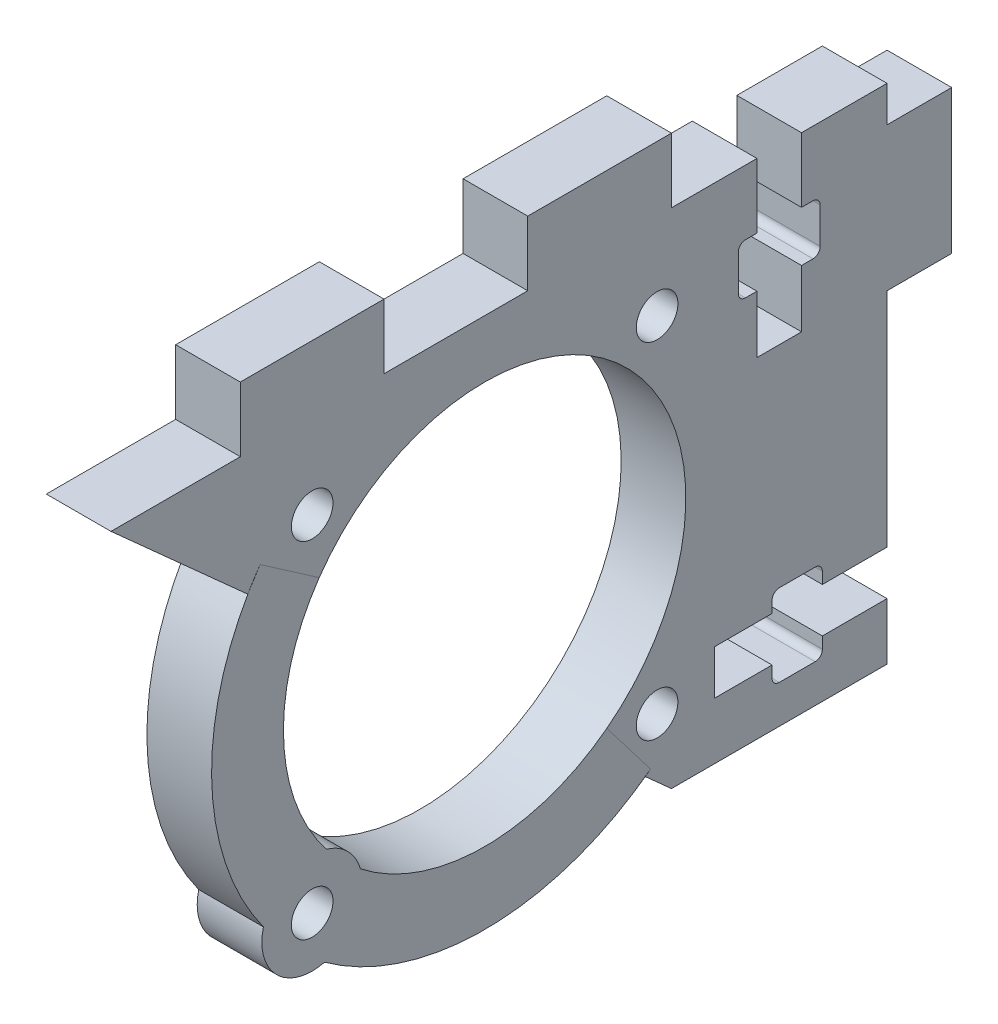
SolidWorks part; units mm, degrees
ref_plane "Front Plane" through (0, 0, 0) normal (0, 0, 1) x (1, 0, 0)
ref_plane "Top Plane" through (0, 0, 0) normal (0, 1, 0) x (1, 0, 0)
ref_plane "Right Plane" through (0, 0, 0) normal (1, 0, 0) x (0, 0, -1)
sketch "Sketch1" plane through (0, 0, 0) normal (1, 0, 0) x (0, 0, -1)
  line L0 (0, 0) -> (0, -35)
  line L1 (0, -35) -> (-54, 0)
  line L2 (-54, 0) -> (0, 0)
  dimension "D1" = 35
  dimension "D2" = 54
extrude "Boss-Extrude1" add sketch "Sketch1" along normal blind 4.5
sketch "Sketch2" plane through (4.5, 0, 0) normal (1, 0, 0) x (0, 0, -1)
  line L0 (0, -35) -> (0, 0) construction
  line L1 (-4.5, -2.5) -> (4.5, -2.5)
  line L2 (-4.5, -2.5) -> (-4.5, -12.5)
  line L3 (-4.5, -12.5) -> (4.5, -12.5)
  line L4 (4.5, -2.5) -> (4.5, -12.5)
  line L5 (-4.5, -2.5) -> (4.5, -12.5) construction
  line L6 (-4.5, -12.5) -> (4.5, -2.5) construction
  line L7 (0, 0) -> (-54, 0) construction
  point P0 (0, -7.5)
  dimension "D1" = 10
  dimension "D2" = 7.5
  dimension "D3" = 4.5
extrude "Boss-Extrude2" add sketch "Sketch2" against normal through all
sketch "Sketch3" plane through (4.5, 0, 0) normal (1, 0, 0) x (0, 0, -1)
  line L0 (0, -35) -> (-15, -35)
  line L1 (0, -25) -> (-54, 0)
  line L4 (0, -35) -> (0, -12.5) construction
  line L5 (0, -25) -> (0, -35)
  line L6 (-54, 0) -> (-15, -35)
  dimension "D1" = 15
  dimension "D2" = 10
extrude "Boss-Extrude3" add sketch "Sketch3" against normal through all
sketch "Sketch4" plane through (4.5, 0, 0) normal (1, 0, 0) x (0, 0, -1)
  line L0 (0, -29.5) -> (-12, -29.5) construction
  line L1 (0, -35) -> (0, -12.5) construction
  line L2 (0, -27.95) -> (-12, -27.95) construction
  line L3 (-12, -27.95) -> (-12, -31.05) construction
  line L4 (0, -31.05) -> (0, -27.95)
  line L5 (0, -27.95) -> (-4.5, -27.95)
  line L6 (-4.5, -27.95) -> (-4.5, -27.15)
  line L7 (-5, -26.65) -> (-7.5, -26.65)
  line L8 (-8, -27.15) -> (-8, -27.95)
  line L9 (-8, -27.95) -> (-12, -27.95)
  line L10 (-12, -27.95) -> (-12, -31.05)
  line L12 (0, -31.05) -> (-12, -31.05) construction
  line L13 (-8, -31.05) -> (-12, -31.05)
  line L14 (-8, -31.85) -> (-8, -31.05)
  line L15 (-5, -32.35) -> (-7.5, -32.35)
  line L16 (-4.5, -31.05) -> (-4.5, -31.85)
  line L17 (0, -31.05) -> (-4.5, -31.05)
  line L18 (4.5, -12.5) -> (4.5, -2.5) construction
  line L19 (0, -18.5) -> (-33.3857, -18.5) construction
  line L20 (-54, 0) -> (-15, -35) construction
  line L37 (0, -31.05) -> (-12, -31.05) construction
  arc A0 (-8, -31.85) -> (-7.5, -32.35) centre (-7.5, -31.85) ccw
  arc A1 (-5, -32.35) -> (-4.5, -31.85) centre (-5, -31.85) ccw
  arc A2 (-4.5, -27.15) -> (-5, -26.65) centre (-5, -27.15) ccw
  arc A3 (-7.5, -26.65) -> (-8, -27.15) centre (-7.5, -27.15) ccw
  point P10 (4.5, -7.5)
  point P20 (-8, -32.35)
  point P23 (-4.5, -32.35)
  point P26 (-4.5, -26.65)
  point P29 (-8, -26.65)
  dimension "D7" = 0.5
  dimension "D1" = 12
  dimension "D2" = 1.55
  dimension "D3" = 2.85
  dimension "D4" = 3.5
  dimension "D5" = 8
  dimension "D6" = 22
extrude "Cut-Extrude1" cut sketch "Sketch4" against normal through all
sketch "Sketch5" plane through (4.5, 0, 0) normal (1, 0, 0) x (0, 0, -1)
  line L0 (0, 0) -> (-54, 0) construction
  line L1 (-25, 4.5) -> (-15, 4.5)
  line L2 (-25, 4.5) -> (-25, 0)
  line L3 (0, 0) -> (-54, 0) construction
  line L4 (-15, 4.5) -> (-15, 0)
  line L5 (-25, 4.5) -> (-20, 0) construction
  line L6 (-20, 0) -> (-15, 4.5) construction
  line L7 (-30, 0) -> (-30, 4.5) construction
  line L8 (-40, 0) -> (-45, 4.5) construction
  line L9 (-35, 4.5) -> (-40, 0) construction
  line L10 (-45, 4.5) -> (-45, 0)
  line L12 (-35, 4.5) -> (-35, 0)
  line L13 (-35, 4.5) -> (-45, 4.5)
  line L14 (-20, 0) -> (-15, 4.5) construction
  line L15 (-15, 0) -> (-25, 0)
  line L16 (-35, 0) -> (-45, 0)
  point P0 (-20, 0)
  point P14 (-40, 0)
  dimension "D3" = 4.5
  dimension "D1" = 20
  dimension "D2" = 10
  dimension "D4" = 20
  dimension "D5" = 5
extrude "Boss-Extrude4" add sketch "Sketch5" against normal through all
sketch "Sketch8" [suppressed] plane through (4.5, 0, 0) normal (1, 0, 0) x (0, 0, -1)
  line L0 (-15, -30) -> (-27, -30) construction
  line L1 (-15, -35) -> (-27, -35)
  line L2 (-15, -25) -> (-27, -25)
  line L3 (-15, -35) -> (0, -35) construction
  line L4 (-15, -25) -> (-15, -35)
  arc A1 (-27, -25) -> (-27, -35) centre (-27, -30) ccw
  dimension "D5" = 5
  dimension "D1" = 0
  dimension "D2" = 12
  dimension "D3" = 0
  dimension "D4" = 10
extrude "Boss-Extrude5" [suppressed] add sketch "Sketch8" against normal up to surface (4.5 mm away) up to face at (0, -17.3125, 11.9375)
sketch "Sketch9" [suppressed] plane through (4.5, 0, 0) normal (1, 0, 0) x (0, 0, -1)
  line L0 (-27, -30) -> (-22, -30) construction
  line L1 (-27, -27) -> (-22, -27)
  line L2 (-27, -33) -> (-22, -33)
  arc A0 (-27, -27) -> (-27, -33) centre (-27, -30) ccw
  arc A1 (-22, -33) -> (-22, -27) centre (-22, -30) ccw
  point P3 (-24.5, -30)
  dimension "D1" = 3
  dimension "D2" = 5
extrude "Cut-Extrude3" [suppressed] cut sketch "Sketch9" against normal through all
sketch "Sketch10" plane through (0, 0, 0) normal (-1, 0, 0) x (0, 0, 1)
  line L0 (15, -35) -> (54, -12)
  line L1 (54, -12) -> (54, 0)
  line L3 (54, 0) -> (15, -35)
  dimension "D1" = 12
extrude "Boss-Extrude6" [suppressed] add sketch "Sketch10" against normal through all
sketch "Sketch6" plane through (4.5, 0, 0) normal (1, 0, 0) x (0, 0, -1)
  line L0 (-30, 0) -> (-30, -11) construction
  line L1 (-25, 0) -> (-35, 0) construction
  line L2 (-28.45, -11) -> (-31.55, -11) construction
  line L3 (-31.55, -11) -> (-31.55, 0) construction
  line L4 (-28.45, 0) -> (-31.55, 0)
  line L5 (-31.55, 0) -> (-31.55, -4.5)
  line L6 (-31.55, -4.5) -> (-32.35, -4.5)
  line L7 (-32.85, -5) -> (-32.85, -7.5)
  line L8 (-32.35, -8) -> (-31.55, -8)
  line L9 (-31.55, -8) -> (-31.55, -11)
  line L10 (-31.55, -11) -> (-28.45, -11)
  line L11 (-28.45, -11) -> (-28.45, 0) construction
  line L12 (-28.45, -8) -> (-28.45, -11)
  line L13 (-27.65, -8) -> (-28.45, -8)
  line L14 (-27.15, -5) -> (-27.15, -7.5)
  line L15 (-28.45, -4.5) -> (-27.65, -4.5)
  line L16 (-28.45, 0) -> (-28.45, -4.5)
  arc A0 (-32.85, -7.5) -> (-32.35, -8) centre (-32.35, -7.5) ccw
  arc A1 (-32.35, -4.5) -> (-32.85, -5) centre (-32.35, -5) ccw
  arc A2 (-27.65, -4.5) -> (-27.15, -5) centre (-27.65, -5) cw
  arc A3 (-27.15, -7.5) -> (-27.65, -8) centre (-27.65, -7.5) cw
  point P12 (-32.85, -8)
  point P15 (-32.85, -4.5)
  point P26 (-27.15, -4.5)
  point P27 (-27.15, -8)
  dimension "D2" = 1.55
  dimension "D4" = 3.5
  dimension "D6" = 0.5
  dimension "D1" = 11
  dimension "D3" = 8
  dimension "D5" = 2.85
extrude "Cut-Extrude2" [suppressed] cut sketch "Sketch6" against normal through all
sketch "Sketch11" plane through (0, 0, 0) normal (-1, 0, 0) x (0, 0, 1)
  line L0 (7.5, 0) -> (7.5, -12) construction
  line L1 (0, 0) -> (15, 0) construction
  line L2 (5.95, -12) -> (9.05, -12)
  line L3 (9.05, -12) -> (9.05, -8)
  line L4 (9.05, -8) -> (9.85, -8)
  line L5 (10.35, -7.5) -> (10.35, -5)
  line L6 (9.85, -4.5) -> (9.05, -4.5)
  line L7 (9.05, -4.5) -> (9.05, 0)
  line L8 (9.05, 0) -> (5.95, 0)
  line L9 (9.05, -8) -> (9.05, -4.5) construction
  line L10 (0, 0) -> (15, 0) construction
  line L11 (5.95, -8) -> (5.95, -4.5) construction
  line L12 (5.95, -4.5) -> (5.95, 0)
  line L13 (5.15, -4.5) -> (5.95, -4.5)
  line L14 (4.65, -7.5) -> (4.65, -5)
  line L15 (5.95, -8) -> (5.15, -8)
  line L16 (5.95, -12) -> (5.95, -8)
  arc A0 (10.35, -5) -> (9.85, -4.5) centre (9.85, -5) ccw
  arc A1 (5.15, -4.5) -> (4.65, -5) centre (5.15, -5) ccw
  arc A2 (9.85, -8) -> (10.35, -7.5) centre (9.85, -7.5) ccw
  arc A3 (4.65, -7.5) -> (5.15, -8) centre (5.15, -7.5) ccw
  point P11 (7.5, 0)
  point P22 (10.35, -4.5)
  point P25 (4.65, -4.5)
  point P28 (10.35, -8)
  point P31 (4.65, -8)
  dimension "D7" = 0.5
  dimension "D1" = 12
  dimension "D3" = 2.85
  dimension "D8" = 0.5
  dimension "D2" = 3.5
  dimension "D4" = 8
  dimension "D5" = 1.55
  dimension "D6" = 0
extrude "Cut-Extrude4" cut sketch "Sketch11" against normal through all
sketch "Sketch12" plane through (0, 0, 0) normal (-1, 0, 0) x (0, 0, 1)
  line L0 (28, -18) -> (16, -6) construction
  line L1 (28, -18) -> (28, -4) construction
  line L2 (28, -18) -> (40, -6) construction
  line L3 (28, -18) -> (14, -18) construction
  line L4 (28, -18) -> (16, -30) construction
  line L5 (28, -18) -> (16, -6) construction
  line L6 (0, -27.95) -> (0, -12.5) construction
  line L7 (25, 0) -> (35, 0) construction
  circle A0 centre (28, -18) radius 14
  circle A1 centre (16, -6) radius 1.45
  circle A2 centre (40, -6) radius 1.45
  circle A3 centre (16, -30) radius 1.45
  dimension "D1" = 28
  dimension "D2" = 2.9
  dimension "D3" = 12
  dimension "D4" = 45
  dimension "D5" = 28
  dimension "D6" = 18
extrude "FanCutout" cut sketch "Sketch12" against normal through all
sketch "Sketch13" plane through (0, 0, 0) normal (-1, 0, 0) x (0, 0, 1)
  line L0 (39.5107, -10.0311) -> (43.6217, -7.185)
  line L1 (19.4957, -29.121) -> (16.4584, -33.0928)
  line L6 (28, -18) -> (54, 0) construction
  line L7 (28, -18) -> (15, -35) construction
  arc A0 (19.4957, -29.121) -> (39.5107, -10.0311) centre (28, -18) ccw
  arc A1 (16.4584, -33.0928) -> (43.6217, -7.185) centre (28, -18) ccw
  arc A3 (40.643, -11.9871) -> (20.6593, -29.9212) centre (28, -18) ccw construction
  dimension "D1" = 5
extrude "Boss-Extrude7" add sketch "Sketch13" against normal through all
sketch "Sketch14" plane through (0, 0, 0) normal (-1, 0, 0) x (0, 0, 1)
  line L0 (28, -4) -> (28, -32) construction
  line L1 (28, -18) -> (40, -30) construction
  circle A0 centre (28, -18) radius 14 construction
  circle A1 centre (40, -30) radius 3.5
  dimension "D2" = 7
  dimension "D1" = 45
  dimension "D3" = 12
extrude "Boss-Extrude8" add sketch "Sketch14" against normal through all
sketch "Sketch15" plane through (0, 0, 0) normal (-1, 0, 0) x (0, 0, 1)
  line L0 (42.4749, -32.4749) -> (28, -18) construction
  arc A0 (39.1388, -33.3924) -> (43.3924, -29.1388) centre (40, -30) ccw construction
  circle A1 centre (40, -30) radius 1.45
  dimension "D1" = 2.9
extrude "Cut-Extrude6" cut sketch "Sketch15" against normal through all
sketch "Sketch16" [suppressed] plane through (4.5, 0, 0) normal (1, 0, 0) x (0, 0, -1)
  line L0 (0, -34.5) -> (-39, -34.5) construction
  line L1 (0, -27.95) -> (0, -12.5) construction
  line L2 (-15, -34.5) -> (-39, -34.5) construction
  line L3 (-15, -38.5) -> (-39, -38.5)
  line L4 (-15, -30.5) -> (-39, -30.5)
  arc A0 (-15, -38.5) -> (-15, -30.5) centre (-15, -34.5) ccw
  arc A1 (-39, -30.5) -> (-39, -38.5) centre (-39, -34.5) ccw
  point P5 (-27, -34.5)
  point P12 (0, -20.225)
  dimension "D1" = 4
  dimension "D2" = 34.5
  dimension "D3" = 39
  dimension "D4" = 15
extrude "Boss-Extrude9" [suppressed] add sketch "Sketch16" against normal through all
sketch "Sketch17" [suppressed] plane through (4.5, 0, 0) normal (1, 0, 0) x (0, 0, -1)
  line L0 (-43, -34.5) -> (0, -34.5) construction
  line L1 (0, -27.75) -> (0, -12.5) construction
  line L2 (-26.5, -34.5) -> (-26.5, -20.0064) construction
  arc A0 (-42.1823, -32.0766) -> (-39, -38.5) centre (-39, -34.5) ccw construction
  circle A1 centre (-39, -34.5) radius 1.55
  circle A2 centre (-14, -34.5) radius 1.55
  dimension "D1" = 2.9
  dimension "D2" = 12.5
extrude "Cut-Extrude7" [suppressed] cut sketch "Sketch17" against normal through all
sketch "Sketch18" [suppressed] plane through (4.5, 0, 0) normal (1, 0, 0) x (0, 0, -1)
  line L0 (-15, -38.5) -> (0, -35)
  line L1 (0, -35) -> (-11.0314, -35)
  line L2 (-11.0314, -35) -> (-15, -38.5)
extrude "Boss-Extrude10" [suppressed] add sketch "Sketch18" against normal through all
sketch "Sketch20" [suppressed] plane through (4.5, 0, 0) normal (1, 0, 0) x (0, 0, -1)
  line L0 (0, -35) -> (0, -31.05) construction
  line L1 (-9, -38) -> (-37.9081, -38)
  line L2 (-40.7232, -36.0371) -> (-54, 0)
  line L3 (-54, 0) -> (-15, -35)
  line L4 (-15, -35) -> (-6, -35)
  line L5 (-9, -38) -> (-6, -35)
  line L6 (-40.7232, -36.0371) -> (-40, -38) construction
  line L7 (-40, -38) -> (-37.9081, -38) construction
  arc A1 (-37.9081, -38) -> (-40.7232, -36.0371) centre (-37.9081, -35) cw
  point P0 (0, -33.025)
  point P14 (-40, -38)
  dimension "D3" = 6
  dimension "D4" = 3
  dimension "D1" = 40
  dimension "D2" = 3
  dimension "D5" = 135
extrude "Boss-Extrude11" [suppressed] add sketch "Sketch20" against normal through all
sketch "Sketch21" [suppressed] plane through (4.5, 0, 0) normal (1, 0, 0) x (0, 0, -1)
  line L0 (0, -34.5) -> (-41.2895, -34.5) construction
  line L1 (0, -35) -> (0, -31.05) construction
  line L2 (-54, 0) -> (-40.7232, -36.0371) construction
  line L3 (0, -27.95) -> (0, -12.5) construction
  circle A0 centre (-36, -34.5) radius 1.45
  circle A1 centre (-11, -34.5) radius 1.45
  dimension "D2" = 2.9
  dimension "D3" = 2.9
  dimension "D1" = 25
  dimension "D4" = 34.5
  dimension "D5" = 11
extrude "Cut-Extrude8" [suppressed] cut sketch "Sketch21" against normal through all
sketch "Sketch22" [suppressed] plane through (4.5, 0, 0) normal (1, 0, 0) x (0, 0, -1)
  line L0 (0, -27.95) -> (0, -12.5) construction
  line L1 (-25, 0) -> (-35, 0) construction
  circle A0 centre (-28, -18) radius 13.25
  dimension "D2" = 18
  dimension "D3" = 26.5
  dimension "D1" = 28
extrude "Cut-Extrude9" [suppressed] cut sketch "Sketch22" against normal through all
equation "\"X-ROD-SPACING\"=45"
equation "\"Y-ROD-SPACING\"=75"
equation "\"Z-ROD-SPACING\"=17.5"
equation "\"Y-BED-OFFSET\"=2"
equation "\"Y-BED-ROD-INSET\"=3.5"
equation "\"Y-BED-SCREW-SPACING\"=209"
equation "\"Y-BED-SCREW-CUTOUT-SLOT-HEIGHT\"=2"
equation "\"T-SLOT-NUT-FILLET-RADIUS\"=0.5"
equation "\"T-SLOT-SCREW-SHAFT-RADIUS\"=1.55"
equation "\"T-SLOT-SCREW-SHAFT-CUTOUT-LENGTH\"=11.0"
equation "\"T-SLOT-NUT-DEPTH\"=3.5"
equation "\"T-SLOT-NUT-WIDTH\"=2.85"
equation "\"T-SLOT-NUT-END-DISTANCE\"=8"
equation "\"ACRYLIC-THICKNESS\"=10"
equation "\"ACRYLIC-THICKNESS2\"=4.5"
equation "\"ACRYLIC-TAB-CUTOUT-SIZE\"=\"ACRYLIC-THICKNESS\"+\"ACRYLIC-TAB-TOLERANCE\"*2"
equation "\"ACRYLIC-TAB-WIDTH\"=\"ACRYLIC-THICKNESS\""
equation "\"ACRYLIC-M3-HOLE\"=2.9"
equation "\"SMOOTHROD-CAP-SCREW-DISTANCE\"=20"
equation "\"FRAME-WIDTH-INNER\"=370"
equation "\"NEMA17-HOLE-SPACING\"=31"
equation "\"NEMA17-CENTRAL-CUTOUT\"=22.5"
equation "\"Z-BRACKET-REACH\"=55"
equation "\"Z-ROD-INSET\"=16"
equation "\"TOP-BRACKET-SPACING\"=40"
equation "\"SMOOTHROD-X-LENGTH\"=350"
equation "\"SMOOTHROD-Y-LENGTH\"=350"
equation "\"SMOOTHROD-Z-LENGTH\"=350"
equation "\"SMOOTHROD-TIGHTENING-HEADROOM\"=.25"
equation "\"LEADSCREW-Z-LENGTH\"=300"
equation "\"SCREW-LENGTH-FRAME\"=\"ACRYLIC-THICKNESS\" + 10"
equation "\"SCREW-LENGTH-MOTOR\"=\"ACRYLIC-THICKNESS\" + 5"
equation "\"SCREW-LENGTH-EXTRUDER\"=28"
equation "\"SCREW-HEAD-RADIUS\"=6"
equation "\"PRINTED-X-SMOOTHROD-DIAMETER\"=8.4"
equation "\"PRINTED-X-SMOOTHROD-CUTOUT\"=10"
equation "\"PRINTED-X-BASE-HEIGHT\"=10"
equation "\"PRINTED-LM8UU-CUTOUT-SIZE\"=15.5"
equation "\"PRINTED-LM8UU-CUTOUT-LENGTH\"=24.5"
equation "\"PRINTED-X-IDLER-HEIGHT\"=16"
equation "\"PSU-MOUNTING-WIDTH\"=95"
equation "\"PSU-MOUNTING-HEIGHT\"=177"
equation "\"Y-BELT-TO-ROD-DISTANCE\"=20"
equation "\"SPOOL-HOLDER-ROD-SPACING\"=150"
equation "\"ACRYLIC-X-CARRIAGE-WIDTH\"=55"
equation "\"ACRYLIC-X-CARRIAGE-HEIGHT\"=75"
equation "\"ACRYLIC-X-CARRIAGE-SCREW-SPACING-X\"=15"
equation "\"ACRYLIC-X-CARRIAGE-SCREW-SPACING-Y\"=33"
equation "\"ACRYLIC-X-CARRIAGE-CENTER-TAB-SPACING\"=14"
equation "\"ACRYLIC-X-CARRIAGE-EXTRUDER-SHELF-DEPTH\"=\"ACRYLIC-X-CARRIAGE-EXTRUDER-OFFSET\" + 28"
equation "\"D2@Sketch1\"=\"ACRYLIC-X-CARRIAGE-EXTRUDER-SHELF-DEPTH\""
equation "\"D1@Boss-Extrude1\"=\"ACRYLIC-THICKNESS2\""
equation "\"D1@Sketch2\"=\"ACRYLIC-TAB-WIDTH\""
equation "\"D3@Sketch2\"=\"ACRYLIC-THICKNESS2\""
equation "\"ACRYLIC-X-CARRIAGE-LM8UU-CUTOUT-WIDTH\"=24.25"
equation "\"ACRYLIC-X-CARRIAGE-EXTRUDER-BRACE-SPACING\"=23"
equation "\"ACRYLIC-X-CARRIAGE-EXTRUDER-BRACE-HEIGHT\"=35"
equation "\"D1@Sketch1\"=\"ACRYLIC-X-CARRIAGE-EXTRUDER-BRACE-HEIGHT\""
equation "\"D1@Sketch4\"=\"T-SLOT-SCREW-SHAFT-CUTOUT-LENGTH\"+1"
equation "\"D2@Sketch4\"=\"T-SLOT-SCREW-SHAFT-RADIUS\""
equation "\"D3@Sketch4\"=\"T-SLOT-NUT-WIDTH\""
equation "\"D4@Sketch4\"=\"T-SLOT-NUT-DEPTH\""
equation "\"D5@Sketch4\"=\"T-SLOT-NUT-END-DISTANCE\""
equation "\"D7@Sketch4\"=\"T-SLOT-NUT-FILLET-RADIUS\""
equation "\"ACRYLIC-X-CARRIAGE-EXTRUDER-BRACE-SCREW-SPACING\"=22"
equation "\"D6@Sketch4\"=\"ACRYLIC-X-CARRIAGE-EXTRUDER-BRACE-SCREW-SPACING\""
equation "\"ACRYLIC-X-CARRIAGE-EXTRUDER-BRACE-TAB-OFFSET\"=20"
equation "\"D1@Sketch5\"=\"ACRYLIC-X-CARRIAGE-EXTRUDER-BRACE-TAB-OFFSET\""
equation "\"D2@Sketch5\"=\"ACRYLIC-TAB-WIDTH\""
equation "\"D3@Sketch5\"=\"ACRYLIC-THICKNESS2\""
equation "\"ACRYLIC-X-CARRIAGE-EXTRUDER-OFFSET\"=26"
equation "\"ACRYLIC-X-CARRIAGE-EXTRUDER-ANGLE\"=90"
equation "\"D1@Sketch6\"=\"T-SLOT-SCREW-SHAFT-CUTOUT-LENGTH\""
equation "\"D2@Sketch6\"=\"T-SLOT-SCREW-SHAFT-RADIUS\""
equation "\"D3@Sketch6\"=\"T-SLOT-NUT-END-DISTANCE\""
equation "\"D4@Sketch6\"=\"T-SLOT-NUT-DEPTH\""
equation "\"D5@Sketch6\"=\"T-SLOT-NUT-WIDTH\""
equation "\"D6@Sketch6\"=\"T-SLOT-NUT-FILLET-RADIUS\""
equation "\"D1@Sketch11\"=\"T-SLOT-SCREW-SHAFT-CUTOUT-LENGTH\"+1"
equation "\"D2@Sketch11\"=\"T-SLOT-NUT-DEPTH\""
equation "\"D3@Sketch11\"=\"T-SLOT-NUT-WIDTH\""
equation "\"D4@Sketch11\"=\"T-SLOT-NUT-END-DISTANCE\""
equation "\"D5@Sketch11\"=\"T-SLOT-SCREW-SHAFT-RADIUS\""
equation "\"D7@Sketch11\"=\"T-SLOT-NUT-FILLET-RADIUS\""
equation "\"D8@Sketch11\"=\"T-SLOT-NUT-FILLET-RADIUS\""
equation "\"D2@Sketch12\"=\"ACRYLIC-M3-HOLE\""
equation "\"D1@Sketch15\"=\"ACRYLIC-M3-HOLE\""
equation "\"D1@Sketch17\"=\"ACRYLIC-M3-HOLE\""
equation "\"D2@Sketch21\"=\"ACRYLIC-M3-HOLE\""
equation "\"D3@Sketch21\"=\"ACRYLIC-M3-HOLE\""
